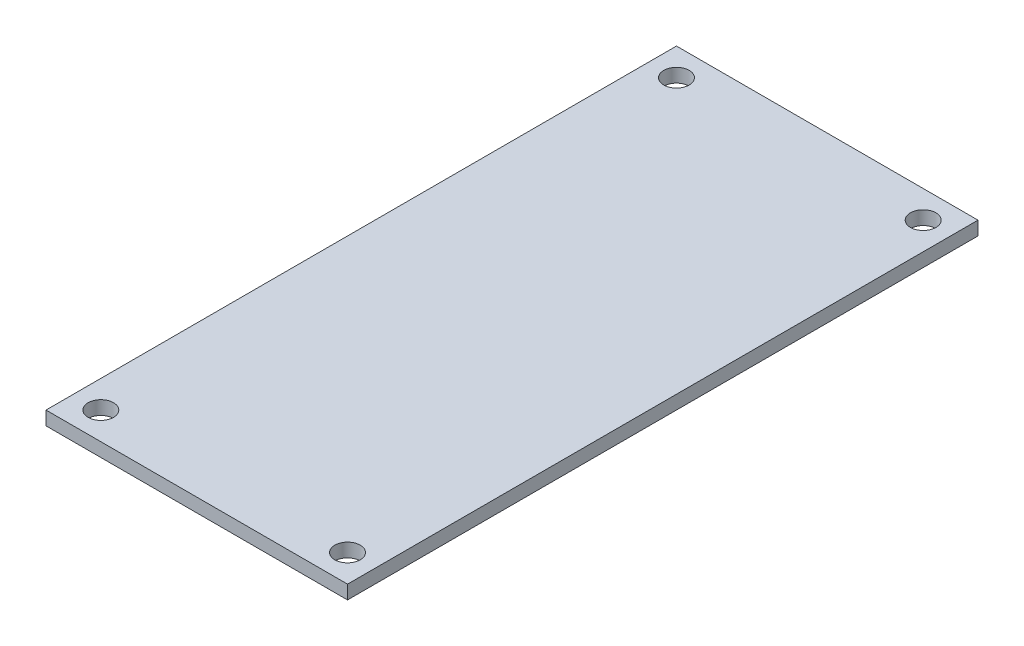
SolidWorks part; units mm, degrees
ref_plane "Front Plane" through (0, 0, 0) normal (0, 0, 1) x (1, 0, 0)
ref_plane "Top Plane" through (0, 0, 0) normal (0, 1, 0) x (1, 0, 0)
ref_plane "Right Plane" through (0, 0, 0) normal (1, 0, 0) x (0, 0, -1)
sketch "Sketch1" plane through (0, 0, 0) normal (0, 1, 0) x (1, 0, 0)
  line L1 (0, 0) -> (34.925, 0)
  line L2 (0, 0) -> (0, 73.025)
  line L3 (0, 73.025) -> (34.925, 73.025)
  line L4 (34.925, 0) -> (34.925, 73.025)
  line L5 (3.175, 69.85) -> (31.75, 69.85) construction
  line L6 (3.175, 69.85) -> (3.175, 3.175) construction
  line L7 (3.175, 3.175) -> (31.75, 3.175) construction
  line L8 (31.75, 69.85) -> (31.75, 3.175) construction
  circle A0 centre (3.175, 69.85) radius 1.4732
  circle A1 centre (31.75, 69.85) radius 1.4732
  circle A2 centre (3.175, 3.175) radius 1.4732
  circle A3 centre (31.75, 3.175) radius 1.4732
  dimension "D7" = 2.9464
  dimension "D1" = 73.025
  dimension "D2" = 34.925
  dimension "D3" = 3.175
  dimension "D4" = 3.175
  dimension "D5" = 3.175
  dimension "D6" = 3.175
extrude "Boss-Extrude1" add sketch "Sketch1" along normal blind 1.5875 contours L2 L3 L4 L1
extrude "Cut-Extrude1" cut sketch "Sketch1<4>" along normal blind 1.5875 contours A1 | A0 | A3 | A2 region at (3.175, 0, -69.85) region at (31.75, 0, -69.85) region at (3.175, 0, -3.175) region at (31.75, 0, -3.175)
sketch "Sketch1<4>" plane through (0, 0, 0) normal (0, 1, 0) x (1, 0, 0) same geometry as "Sketch1"
